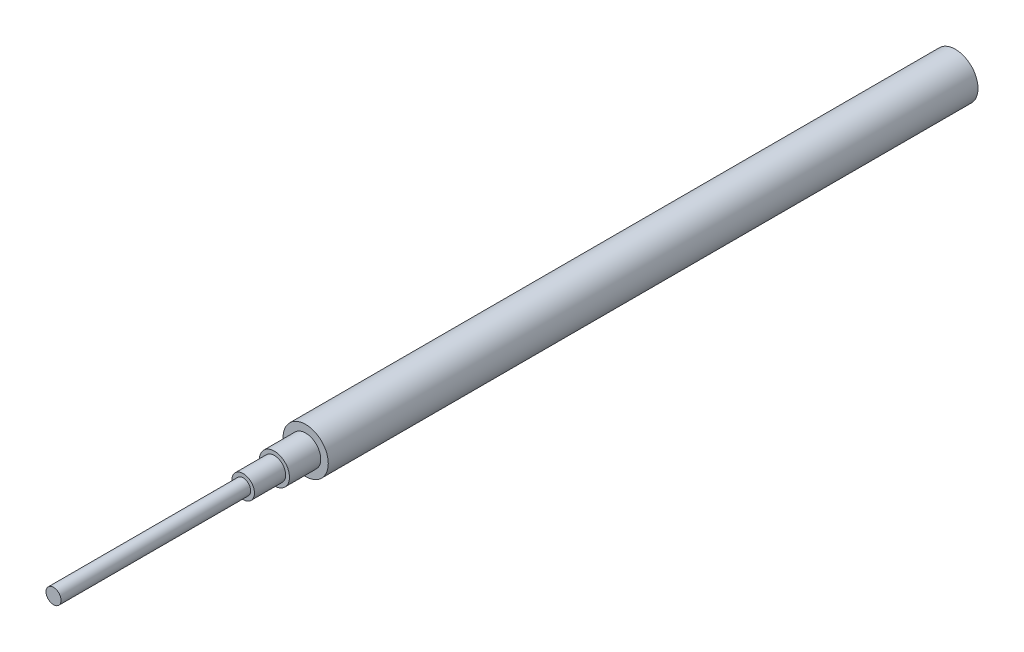
SolidWorks part; units mm, degrees
material "Plain Carbon Steel"
ref_plane "Front Plane" through (0, 0, 0) normal (0, 0, 1) x (1, 0, 0)
ref_plane "Top Plane" through (0, 0, 0) normal (0, 1, 0) x (1, 0, 0)
ref_plane "Right Plane" through (0, 0, 0) normal (1, 0, 0) x (0, 0, -1)
sketch "Sketch1" plane through (0, 0, 0) normal (0, 0, 1) x (1, 0, 0)
  circle A0 centre (0, 0) radius 4.7625
  dimension "D1" = 9.525
extrude "Boss-Extrude1" add sketch "Sketch1" along normal blind 136.88
sketch "Sketch2" plane through (0, 0, 0) normal (0, 0, 1) x (1, 0, 0)
  circle A0 centre (0, 0) radius 3.175
  dimension "D1" = 6.35
extrude "Boss-Extrude2" add sketch "Sketch2" along normal blind 143.47
sketch "Sketch3" plane through (0, 0, 0) normal (0, 0, 1) x (1, 0, 0)
  circle A0 centre (0, 0) radius 2.3812
  dimension "D1" = 4.7625
extrude "Boss-Extrude3" add sketch "Sketch3" along normal blind 150.05
sketch "Sketch4" plane through (0, 0, 0) normal (0, 0, 1) x (1, 0, 0)
  circle A0 centre (0, 0) radius 1.5875
  dimension "D1" = 3.175
extrude "Boss-Extrude4" add sketch "Sketch4" along normal blind 190
ref_axis "Axis1" through (0, 0, -9.5) along (0, 0, 1)
